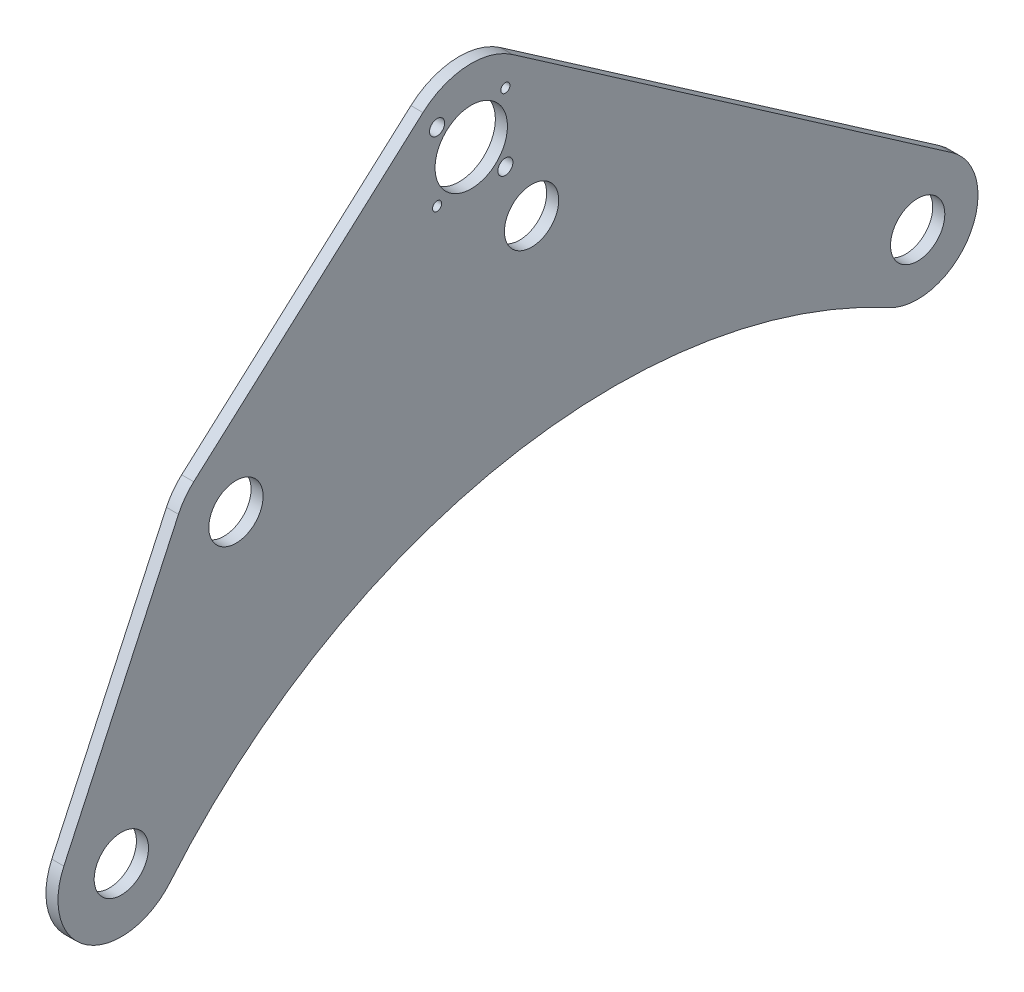
SolidWorks part; units mm, degrees
material "Acrylic (Medium-high impact)"
ref_plane "Front Plane" through (0, 0, 0) normal (0, 0, 1) x (1, 0, 0)
ref_plane "Top Plane" through (0, 0, 0) normal (0, 1, 0) x (1, 0, 0)
ref_plane "Right Plane" through (0, 0, 0) normal (1, 0, 0) x (0, 0, -1)
sketch "Sketch1" plane through (0, 0, 0) normal (1, 0, 0) x (0, 0, -1)
  line L0 (-548.7618, -304.8) -> (152.435, -304.8)
  line L1 (-192.8252, -120.65) -> (-152.4, -120.65)
  line L2 (-234.95, -162.7748) -> (-234.95, -205.5252)
  line L3 (-192.8252, -247.65) -> (-152.4, -247.65)
  line L4 (-152.4, -120.65) -> (-152.4, -247.65)
  circle A1 centre (0, 0) radius 6.35
  circle A6 centre (-419.1, -79.375) radius 9.525
  circle A7 centre (-358.775, 50.8) radius 9.525
  circle A8 centre (-203.2, 107.95) radius 9.525
  arc A9 (-234.95, -205.5252) -> (-192.8252, -247.65) centre (-192.8252, -205.5252) ccw
  arc A10 (-192.8252, -120.65) -> (-234.95, -162.7748) centre (-192.8252, -162.7748) ccw
  circle A11 centre (-358.775, -182.7754) radius 120.65
  circle A12 centre (-234.95, 155.194) radius 29.845
  dimension "D1" = 12.7
  dimension "D2" = 19.05
  dimension "D3" = 42.1248
  dimension "D4" = 127
  dimension "D7" = 184.15
  dimension "D6" = 241.3
  dimension "D16" = 59.69
  dimension "D5" = 82.55
  dimension "D8" = 304.8
  dimension "D9" = 152.4
  dimension "D10" = 419.1
  dimension "D11" = 79.375
  dimension "D12" = 358.775
  dimension "D13" = 50.8
  dimension "D14" = 203.2
  dimension "D15" = 107.95
  dimension "D17" = 234.95
  dimension "D18" = 155.194
sketch "Sketch2" plane through (0, 0, 0) normal (1, 0, 0) x (0, 0, -1)
  line L1 (-449.3475, -65.3579) -> (-389.0225, 64.8171)
  line L3 (-381.0036, 75.6451) -> (-260.3541, 183.5884)
  line L5 (-213.2394, 186.5031) -> (18.0922, 26.0909)
  arc A0 (-381.0036, 75.6451) -> (-389.0225, 64.8171) centre (-358.775, 50.8) ccw
  arc A2 (-449.3475, -65.3579) -> (-393.5233, -100.7578) centre (-419.1, -79.375) ccw
  arc A4 (-213.2394, 186.5031) -> (-260.3541, 183.5884) centre (-234.95, 155.194) ccw
  arc A5 (-15.0641, -27.9488) -> (18.0922, 26.0909) centre (0, 0) ccw
  arc A8 (-393.5233, -100.7578) -> (-15.0641, -27.9488) centre (-159.6794, -296.2573) cw
  circle A12 centre (-419.1, -79.375) radius 9.525 construction
  circle A13 centre (-358.775, 50.8) radius 9.525 construction
  dimension "D1" = 33.3375
  dimension "D2" = 63.5
  dimension "D3" = 76.2
  dimension "D4" = 304.8
extrude "Boss-Extrude1" add sketch "Sketch2" along normal blind 6.35
sketch "Sketch3" plane through (6.35, 0, 0) normal (1, 0, 0) x (0, 0, -1)
  line L0 (-216.9895, 173.1545) -> (-252.9105, 137.2335) construction
  line L1 (-234.95, 155.194) -> (-234.95, 205.0182) construction
  line L2 (-252.9105, 173.1545) -> (-216.9895, 137.2335) construction
  circle A0 centre (-203.2, 107.95) radius 14.2875
  circle A1 centre (-358.775, 50.8) radius 14.2875
  circle A2 centre (-419.1, -79.375) radius 14.2875
  circle A3 centre (-234.95, 155.194) radius 19.05
  circle A4 centre (0, 0) radius 14.2875
  circle A5 centre (-252.9105, 137.2335) radius 2.413
  circle A7 centre (-216.9895, 137.2335) radius 3.9687
  circle A8 centre (-216.9895, 173.1545) radius 2.413
  circle A9 centre (-252.9105, 173.1545) radius 3.9687
  point P18 (-234.95, 155.194)
  point P28 (-234.95, 155.194)
  dimension "D1" = 38.1
  dimension "D2" = 28.575
  dimension "D3" = 4.826
  dimension "D4" = 50.8
  dimension "D5" = 45
  dimension "D6" = 7.9375
  dimension "D7" = 50.8
extrude "Cut-Extrude1" cut sketch "Sketch3" against normal up to next
